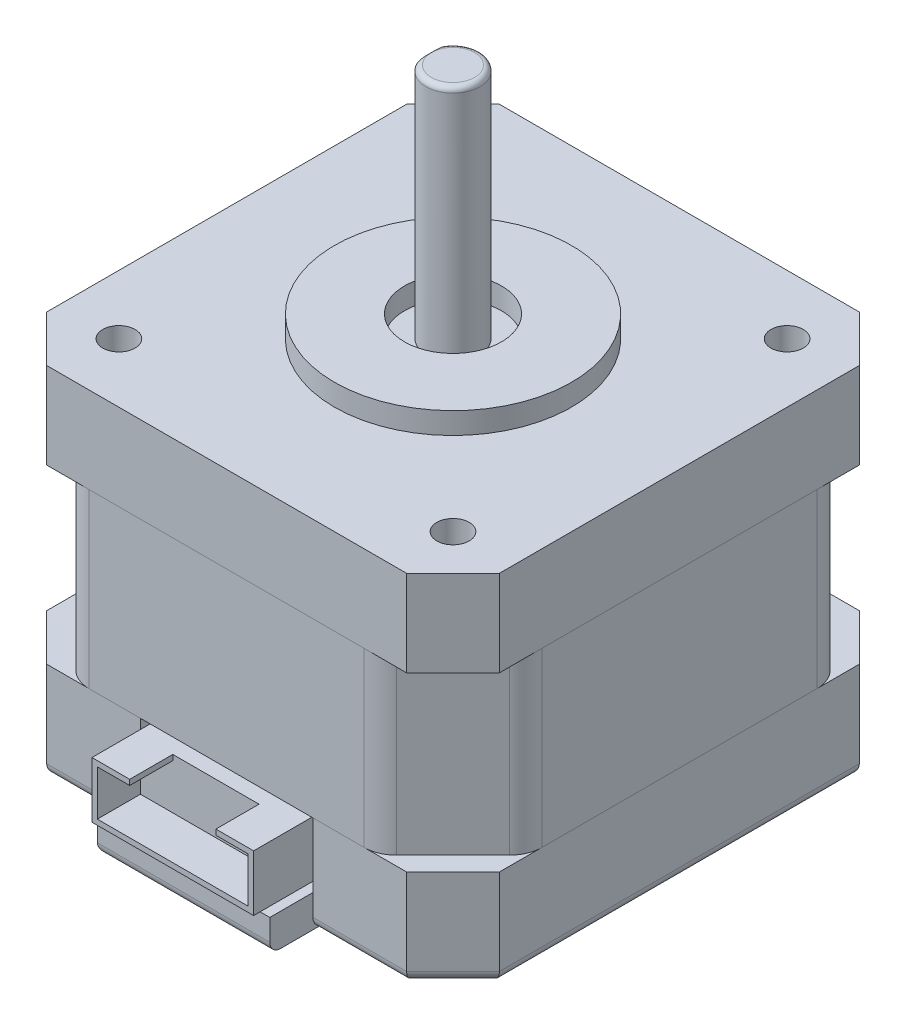
SolidWorks part; units mm, degrees
ref_plane "Front Plane" through (0, 0, 0) normal (0, 0, 1) x (1, 0, 0)
ref_plane "Top Plane" through (0, 0, 0) normal (0, 1, 0) x (1, 0, 0)
ref_plane "Right Plane" through (0, 0, 0) normal (1, 0, 0) x (0, 0, -1)
sketch "Sketch1" plane through (0, 0, 0) normal (0, 1, 0) x (1, 0, 0)
  line L0 (-21, 21) -> (21, -21) construction
  line L1 (-21, 21) -> (21, 21)
  line L2 (-21, 21) -> (-21, -21)
  line L3 (-21, -21) -> (21, -21)
  line L4 (21, 21) -> (21, -21)
  line L5 (-15.5, 15.5) -> (15.5, -15.5) construction
  circle A0 centre (-15.5, 15.5) radius 1.5
  circle A1 centre (15.5, 15.5) radius 1.5
  circle A2 centre (-15.5, -15.5) radius 1.5
  circle A3 centre (15.5, -15.5) radius 1.5
  point P4 (0, 0)
  point P14 (0, 0)
  dimension "D2" = 3
  dimension "D1" = 42
  dimension "D3" = 31
extrude "Boss-Extrude1" add sketch "Sketch1" along normal blind 8
sketch "Sketch2" plane through (0, 0, 0) normal (0, 1, 0) x (1, 0, 0)
  circle A0 centre (0, 0) radius 11
  circle A1 centre (0, 0) radius 4.5
  dimension "D1" = 22
  dimension "D2" = 9
extrude "Boss-Extrude2" add sketch "Sketch2" along normal blind 10
sketch "Sketch3" plane through (0, 0, 0) normal (0, 1, 0) x (1, 0, 0)
  line L0 (21, 21) -> (-21, -21) construction
  line L1 (-21, 21) -> (21, 21)
  line L2 (-21, 21) -> (-21, -21)
  line L3 (-21, -21) -> (21, -21)
  line L4 (21, 21) -> (21, -21)
  point P4 (0, 0)
  dimension "D1" = 42
extrude "Boss-Extrude3" add sketch "Sketch3" against normal blind 16 separate body
ref_plane "Plane1" through (0, -16, 0) normal (0, -1, 0) x (-1, 0, 0)
sketch "Sketch5" plane through (0, -16, 0) normal (0, -1, 0) x (-1, 0, 0)
  line L0 (21, 21) -> (-21, -21) construction
  line L1 (-21, 21) -> (21, 21)
  line L2 (-21, 21) -> (-21, -21)
  line L4 (21, 21) -> (21, -21)
  line L5 (1, 1) -> (-1, -1) construction
  line L6 (8, -21) -> (8, -1)
  line L7 (8, -1) -> (-8, -1)
  line L8 (-8, -1) -> (-8, -21)
  line L9 (21, -21) -> (8, -21)
  line L10 (21, -21) -> (-21, -21) construction
  line L11 (-8, -21) -> (-21, -21)
  point P4 (0, 0)
  point P13 (0, -1)
  point P15 (0, 0)
  dimension "D2" = 16
  dimension "D3" = 20
  dimension "D1" = 42
extrude "Boss-Extrude4" add sketch "Sketch5" along normal blind 9 separate body
chamfer "Chamfer1" distance 4.3 angle 45 4 edges at (-21, 4, -21) (21, 4, -21) (21, 4, 21) (-21, 4, 21)
chamfer "Chamfer5" distance 4.3 angle 45 4 edges at (21, -20.5, -21) (-21, -20.5, -21) (21, -20.5, 21) (-21, -20.5, 21)
chamfer "Chamfer6" distance 7 angle 45 4 edges at (-21, -8, -21) (21, -8, -21) (21, -8, 21) (-21, -8, 21)
fillet "Fillet1" radius 3 8 edges at (21, -8, 14) (14, -8, 21) (-14, -8, 21) (-21, -8, 14) (-21, -8, -14) (-14, -8, -21) (14, -8, -21) (21, -8, -14)
ref_plane "Plane5" through (0, -25, 0) normal (0, -1, 0) x (-1, 0, 0)
sketch "Sketch7" plane through (0, -25, -25) normal (0, 1, 0) x (1, 0, 0)
  line L0 (18.85, -6.15) -> (-18.85, -43.85) construction
  line L5 (16, -9) -> (-16, -41) construction
  line L7 (16.7, -4) -> (21, -8.3) construction
  line L8 (-16, -41) -> (-21, -41) construction
  line L9 (-21, -41.7) -> (-21, -8.3) construction
  line L10 (16, -9) -> (21, -9) construction
  line L11 (21, -8.3) -> (21, -41.7) construction
  line L12 (-16.7, -46) -> (-21, -41.7) construction
  circle A0 centre (16, -41) radius 2.75
  circle A1 centre (-16, -41) radius 2.75
  circle A2 centre (16, -9) radius 2.75
  circle A3 centre (-16, -9) radius 2.75
  point P6 (-18.85, -43.85)
  point P20 (18.85, -6.15)
  dimension "D2" = 32
  dimension "D3" = 5.5
extrude "Cut-Extrude3" cut sketch "Sketch7" along normal blind 3
sketch "Sketch8" plane through (0, -25, 0) normal (0, -1, 0) x (-1, 0, 0)
  line L0 (-16.7, -21) -> (-8, -21) construction
  line L1 (8, 0) -> (-8, 0)
  line L2 (8, 0) -> (8, -25)
  line L3 (8, -25) -> (-8, -25)
  line L4 (-8, 0) -> (-8, -25)
  point P4 (0, 0)
  dimension "D1" = 16
  dimension "D2" = 4
extrude "Boss-Extrude5" add sketch "Sketch8" against normal blind 3
fillet "Fillet2" radius 1 11 edges at (18.85, -25, -18.85) (0, -25, -21) (-18.85, -25, -18.85) (-21, -25, 0) (-18.85, -25, 18.85) (21, -25, 0) (18.85, -25, 18.85) (12.35, -25, 21) (-12.35, -25, 21) (-8, -25, 23) (0, -25, 25)
sketch "Sketch9" plane through (0, 0, 0) normal (0, 0, 1) x (1, 0, 0)
  line L0 (-7, -16.9) -> (-7, -21.1)
  line L2 (-7.5, -16.4) -> (-7.5, -21.6)
  line L3 (-7.5, -21.6) -> (7.5, -21.6)
  line L4 (7.5, -16.4) -> (7.5, -21.6)
  line L5 (-7, -21.1) -> (7, -21.1)
  line L6 (7, -21.1) -> (7, -16.9)
  line L8 (-7, -21.1) -> (-7, -21.6) construction
  line L9 (-7.5, -16.4) -> (-4, -16.4)
  line L10 (-4, -16.4) -> (-4, -16.9)
  line L11 (-4, -16.9) -> (-7, -16.9)
  line L12 (7.5, -16.4) -> (4, -16.4)
  line L13 (4, -16.4) -> (4, -16.9)
  line L14 (4, -16.9) -> (7, -16.9)
  line L15 (7, -21.1) -> (7.5, -21.1) construction
  point P10 (0, -21.6)
  dimension "D1" = 8
  dimension "D2" = 5.2
  dimension "D3" = 15
  dimension "D4" = 16.4
  dimension "D5" = 0.5
extrude "Boss-Extrude6" add sketch "Sketch9" along normal blind 26
sketch "Sketch10" plane through (0, -25, 0) normal (0, -1, 0) x (-1, 0, 0)
  circle A0 centre (0, 0) radius 4.5
  dimension "D1" = 9
extrude "Cut-Extrude4" cut sketch "Sketch10" against normal blind 2
sketch "Sketch11" plane through (0, -23, 0) normal (0, -1, 0) x (1, 0, 0)
  circle A0 centre (0, 0) radius 2
  circle A1 centre (0, 0) radius 2.5
  dimension "D1" = 4
  dimension "D2" = 5
extrude "Cut-Extrude5" cut sketch "Sketch11" against normal blind 0.5
fillet "Fillet3" radius 0.5 1 edges at (0, -23, -2)
fillet "Fillet4" radius 0.5 5 edges at (0, -25, -4.5) (16, -25, 18.75) (16, -25, -13.25) (-16, -25, -13.25) (-16, -25, 18.75)
sketch "Sketch12" plane through (0, -22, 0) normal (0, -1, 0) x (1, 0, 0)
  circle A0 centre (-16, 16) radius 2.5
  circle A1 centre (16, 16) radius 2.5
  circle A2 centre (-16, -16) radius 2.5
  circle A3 centre (16, -16) radius 2.5
  dimension "D1" = 5
extrude "Boss-Extrude7" add sketch "Sketch12" along normal blind 3
fillet "Fillet5" radius 2 4 edges at (16, -25, -18.5) (-16, -25, -18.5) (16, -25, 13.5) (-16, -25, 13.5)
sketch "Sketch13" plane through (0, -25, 0) normal (0, -1, 0) x (-1, 0, 0)
  line L0 (16.5, -14) -> (16.5, -15.5)
  line L1 (16.5, -15.5) -> (18, -15.5)
  line L2 (18, -15.5) -> (18, -16.5)
  line L3 (18, -16.5) -> (16.5, -16.5)
  line L4 (16.5, -16.5) -> (16.5, -18)
  line L5 (16.5, -18) -> (15.5, -18)
  line L6 (15.5, -18) -> (15.5, -16.5)
  line L7 (15.5, -16.5) -> (14, -16.5)
  line L8 (14, -16.5) -> (14, -15.5)
  line L9 (14, -15.5) -> (15.5, -15.5)
  line L10 (15.5, -15.5) -> (15.5, -14)
  line L11 (15.5, -14) -> (16.5, -14)
  line L12 (-15.5, -14) -> (-15.5, -15.5)
  line L13 (-15.5, -15.5) -> (-14, -15.5)
  line L14 (-14, -15.5) -> (-14, -16.5)
  line L15 (-14, -16.5) -> (-15.5, -16.5)
  line L16 (-15.5, -16.5) -> (-15.5, -18)
  line L17 (-15.5, -18) -> (-16.5, -18)
  line L18 (-16.5, -18) -> (-16.5, -16.5)
  line L19 (-16.5, -16.5) -> (-18, -16.5)
  line L20 (-18, -16.5) -> (-18, -15.5)
  line L21 (-18, -15.5) -> (-16.5, -15.5)
  line L22 (-16.5, -15.5) -> (-16.5, -14)
  line L23 (-16.5, -14) -> (-15.5, -14)
  line L24 (-15.5, 18) -> (-15.5, 16.5)
  line L25 (-15.5, 16.5) -> (-14, 16.5)
  line L26 (-14, 16.5) -> (-14, 15.5)
  line L27 (-14, 15.5) -> (-15.5, 15.5)
  line L28 (-15.5, 15.5) -> (-15.5, 14)
  line L29 (-15.5, 14) -> (-16.5, 14)
  line L30 (-16.5, 14) -> (-16.5, 15.5)
  line L31 (-16.5, 15.5) -> (-18, 15.5)
  line L32 (-18, 15.5) -> (-18, 16.5)
  line L33 (-18, 16.5) -> (-16.5, 16.5)
  line L34 (-16.5, 16.5) -> (-16.5, 18)
  line L35 (-16.5, 18) -> (-15.5, 18)
  line L36 (16.5, 18) -> (16.5, 16.5)
  line L37 (16.5, 16.5) -> (18, 16.5)
  line L38 (18, 16.5) -> (18, 15.5)
  line L39 (18, 15.5) -> (16.5, 15.5)
  line L40 (16.5, 15.5) -> (16.5, 14)
  line L41 (16.5, 14) -> (15.5, 14)
  line L42 (15.5, 14) -> (15.5, 15.5)
  line L43 (15.5, 15.5) -> (14, 15.5)
  line L44 (14, 15.5) -> (14, 16.5)
  line L45 (14, 16.5) -> (15.5, 16.5)
  line L46 (15.5, 16.5) -> (15.5, 18)
  line L47 (15.5, 18) -> (16.5, 18)
  circle A0 centre (16, -16) radius 0.7071 construction
  circle A1 centre (-16, -16) radius 0.7071 construction
  circle A2 centre (-16, 16) radius 0.7071 construction
  circle A3 centre (16, 16) radius 0.7071 construction
  circle A4 centre (16, 16) radius 0.5 construction
  dimension "D1" = 1
  dimension "D2" = 1.5
extrude "Cut-Extrude6" cut sketch "Sketch13" against normal blind 2
sketch "Sketch14" plane through (0, 0, 0) normal (0, 1, 0) x (1, 0, 0)
  circle A0 centre (0, 0) radius 2.5
  dimension "D1" = 5
extrude "Boss-Extrude8" add sketch "Sketch14" along normal blind 30
fillet "Fillet6" radius 0.5 1 edges at (0, 30, 2.5)
sketch "Sketch15" plane through (0, 30, 0) normal (0, 1, 0) x (1, 0, 0)
  line L1 (-4, 1.5) -> (-2, 1.5)
  line L2 (-4, 1.5) -> (-4, -1.5)
  line L3 (-4, -1.5) -> (-2, -1.5)
  line L4 (-2, 1.5) -> (-2, -1.5)
  circle A0 centre (0, 0) radius 2.5 construction
  point P4 (-2, 0)
  dimension "D2" = 5
  dimension "D1" = 3
  dimension "D3" = 2
extrude "Cut-Extrude7" cut sketch "Sketch15" against normal blind 18
sketch "Sketch16" plane through (0, 0, 0) normal (0, 0, 1) x (1, 0, 0)
  line L1 (-7.5, -16.4) -> (7.5, -16.4)
  line L2 (-7.5, -16.4) -> (-7.5, -21.6)
  line L3 (-7.5, -21.6) -> (7.5, -21.6)
  line L4 (7.5, -16.4) -> (7.5, -21.6)
extrude "Boss-Extrude9" add sketch "Sketch16" along normal blind 22
